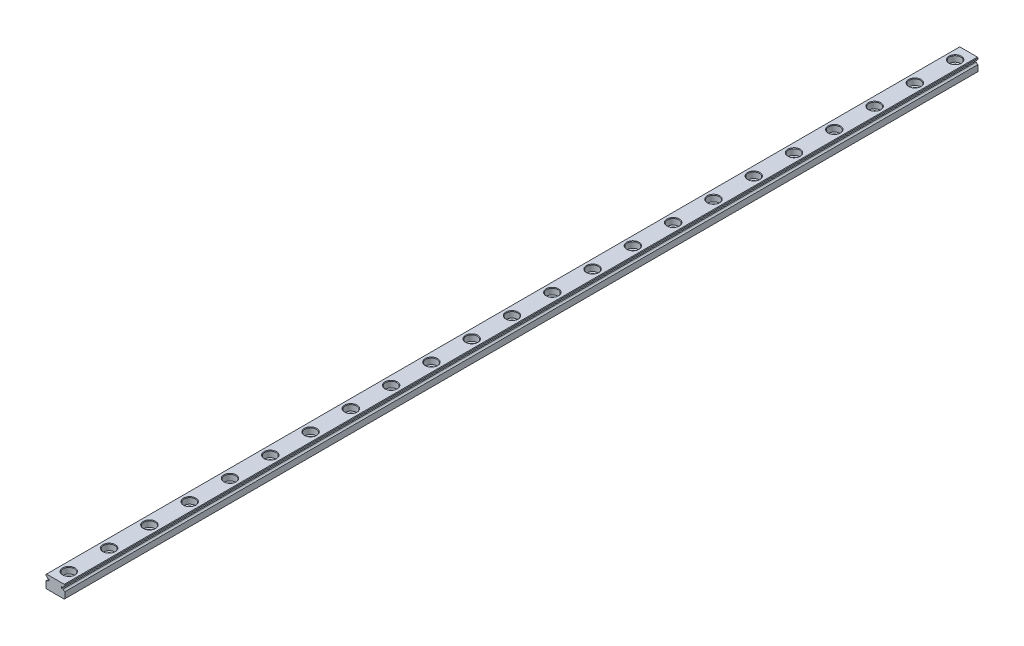
SolidWorks part; units mm, degrees
ref_plane "Спереди" through (0, 0, 0) normal (0, 0, 1) x (1, 0, 0)
ref_plane "Сверху" through (0, 0, 0) normal (0, 1, 0) x (1, 0, 0)
ref_plane "Справа" through (0, 0, 0) normal (1, 0, 0) x (0, 0, -1)
sketch "Sketch1" plane through (0, 0, 0) normal (0, 0, 1) x (1, 0, 0)
  line L0 (0, 0) -> (0, 4.3706) construction
  line L1 (-3.3, -2.4) -> (3.3, -2.4)
  line L2 (-3.5, -2.2) -> (-3.5, 0.1063)
  line L3 (-3.3, 2.4) -> (3.3, 2.4)
  line L4 (3.5, -2.2) -> (3.5, 0.1063)
  line L5 (-3.5, -2.4) -> (3.5, 2.4) construction
  line L6 (-3.5, 2.4) -> (3.5, -2.4) construction
  line L7 (-3.5, 1.6937) -> (-3.5, 2.2)
  line L8 (3.5, 1.6937) -> (3.5, 2.2)
  line L9 (-3.5, -2.2) -> (-3.3, -2.4)
  line L10 (3.3, -2.4) -> (3.5, -2.2)
  line L11 (3.3, 2.4) -> (3.5, 2.2)
  line L12 (-3.5, 2.2) -> (-3.3, 2.4)
  line L13 (2.8401, 0.65) -> (2.3401, 0.65)
  line L14 (-2.8401, 0.65) -> (-2.3401, 0.65)
  line L15 (2.3401, 0.65) -> (2.3401, 1.15)
  line L16 (-2.8401, 1.15) -> (-2.3401, 1.15)
  line L17 (-2.3401, 0.65) -> (-2.3401, 1.15)
  line L18 (2.8401, 1.15) -> (2.3401, 1.15)
  arc A0 (-3.5, 1.6937) -> (-2.8401, 1.15) centre (-3.6, 0.9) cw
  arc A1 (3.5, 1.6937) -> (2.8401, 1.15) centre (3.6, 0.9) ccw
  arc A2 (-2.8401, 0.65) -> (-3.5, 0.1063) centre (-3.6, 0.9) cw
  arc A3 (2.8401, 0.65) -> (3.5, 0.1063) centre (3.6, 0.9) ccw
  point P0 (0, 0)
  dimension "D4" = 0.8
  dimension "D5" = 0.1
  dimension "D1" = 7
  dimension "D2" = 4.8
  dimension "D3" = 1.5
  dimension "D6" = 0.5
  dimension "D7" = 0.5
extrude "Extrude1" add sketch "Sketch1" along normal blind 340
sketch "Sketch2" plane through (0, 2.4, 0) normal (0, 1, 0) x (1, 0, 0)
  line L0 (0, 0) -> (0, -5) construction
  circle A0 centre (0, -5) radius 1.2
  circle A1 centre (0, -5) radius 2.1
  dimension "D1" = 2.4
  dimension "D2" = 4.2
  dimension "D3" = 5
extrude "Extrude2" cut sketch "Sketch2" against normal up to next contours A0 region at (0, 2.4, 5)
extrude "Extrude4" cut sketch "Sketch" against normal blind 2.3
sketch "Sketch" plane through (0, 2.4, 0) normal (0, 1, 0) x (1, 0, 0) same geometry as "Sketch2"
chamfer "Chamfer1" distance 0.2 angle 45 2 edges at (0, -2.4, 6.2) (0, 2.4, 7.1)
pattern_linear "LPattern1" count 23 spacing 15 along (0, 0, 1) of "Extrude4", "Chamfer1", "Extrude2"
